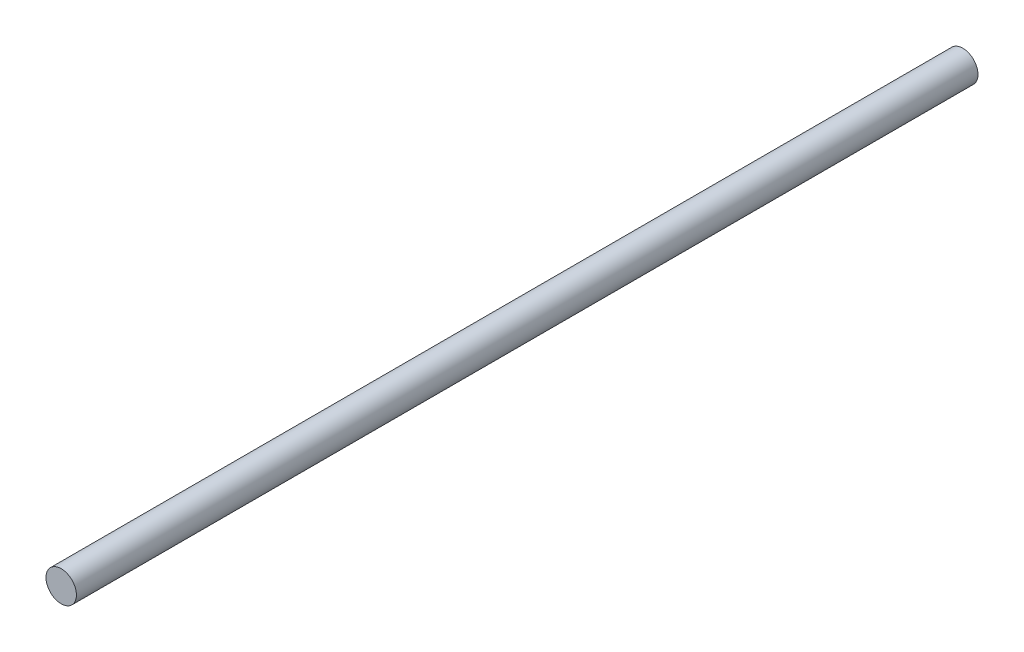
SolidWorks part; units mm, degrees
material "Plain Carbon Steel"
ref_plane "Front Plane" through (0, 0, 0) normal (0, 0, 1) x (1, 0, 0)
ref_plane "Top Plane" through (0, 0, 0) normal (0, 1, 0) x (1, 0, 0)
ref_plane "Right Plane" through (0, 0, 0) normal (1, 0, 0) x (0, 0, -1)
sketch "Sketch1" plane through (0, 0, 0) normal (0, 0, 1) x (1, 0, 0)
  circle A0 centre (0, 0) radius 3.175
  dimension "D1" = 6.35
extrude "Boss-Extrude1" add sketch "Sketch1" along normal blind 188
